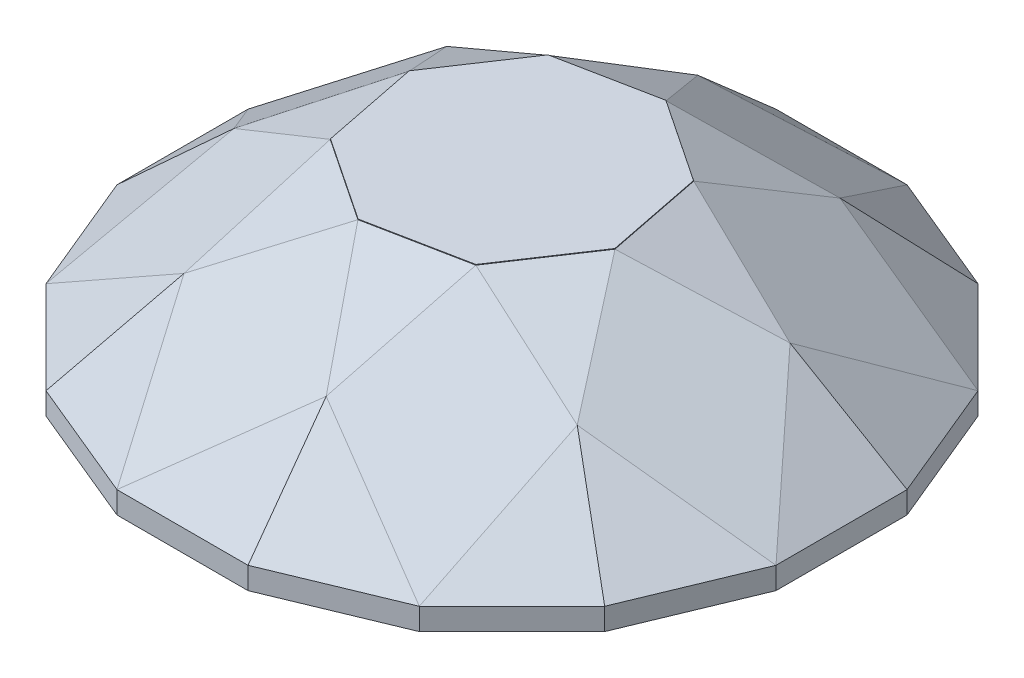
SolidWorks part; units mm, degrees
material "Pure Gold"
ref_plane "Front Plane" through (0, 0, 0) normal (0, 0, 1) x (1, 0, 0)
ref_plane "Top Plane" through (0, 0, 0) normal (0, 1, 0) x (1, 0, 0)
ref_plane "Right Plane" through (0, 0, 0) normal (1, 0, 0) x (0, 0, -1)
sketch "Sketch1" plane through (0, 0, 0) normal (0, 1, 0) x (1, 0, 0)
  line L0 (1.5, 0.2984) -> (1.2716, 0.8497)
  line L1 (-0.8497, -1.2716) -> (-0.2984, -1.5)
  line L2 (-0.2984, -1.5) -> (0.2984, -1.5)
  line L3 (0.2984, -1.5) -> (0.8497, -1.2716)
  line L4 (0.8497, -1.2716) -> (1.2716, -0.8497)
  line L5 (1.2716, -0.8497) -> (1.5, -0.2984)
  line L6 (1.5, -0.2984) -> (1.5, 0.2984)
  line L7 (1.2716, 0.8497) -> (0.8497, 1.2716)
  line L8 (0.8497, 1.2716) -> (0.2984, 1.5)
  line L9 (0.2984, 1.5) -> (-0.2984, 1.5)
  line L10 (-0.2984, 1.5) -> (-0.8497, 1.2716)
  line L11 (-0.8497, 1.2716) -> (-1.2716, 0.8497)
  line L12 (-1.2716, 0.8497) -> (-1.5, 0.2984)
  line L13 (-1.5, 0.2984) -> (-1.5, -0.2984)
  line L14 (-1.5, -0.2984) -> (-1.2716, -0.8497)
  line L15 (-1.2716, -0.8497) -> (-0.8497, -1.2716)
  circle A0 centre (0, 0) radius 1.5 construction
  dimension "D1" = 3
extrude "Boss-Extrude1" add sketch "Sketch1" against normal blind 1 draft 57
sketch "Sketch2" plane through (0, 0, 0) normal (0, 1, 0) x (1, 0, 0)
  line L16 (-1.2716, -0.8497) -> (-0.8497, -1.2716)
  line L17 (-0.8497, -1.2716) -> (-0.2984, -1.5)
  line L18 (-0.2984, -1.5) -> (0.2984, -1.5)
  line L19 (0.2984, -1.5) -> (0.8497, -1.2716)
  line L20 (0.8497, -1.2716) -> (1.2716, -0.8497)
  line L21 (1.2716, -0.8497) -> (1.5, -0.2984)
  line L22 (1.5, -0.2984) -> (1.5, 0.2984)
  line L23 (1.5, 0.2984) -> (1.2716, 0.8497)
  line L24 (1.2716, 0.8497) -> (0.8497, 1.2716)
  line L25 (0.8497, 1.2716) -> (0.2984, 1.5)
  line L26 (0.2984, 1.5) -> (-0.2984, 1.5)
  line L27 (-0.2984, 1.5) -> (-0.8497, 1.2716)
  line L28 (-0.8497, 1.2716) -> (-1.2716, 0.8497)
  line L29 (-1.2716, 0.8497) -> (-1.5, 0.2984)
  line L30 (-1.5, 0.2984) -> (-1.5, -0.2984)
  line L31 (-1.5, -0.2984) -> (-1.2716, -0.8497)
  line L32 (-1.2716, -0.8497) -> (-0.8497, -1.2716)
  line L33 (-0.8497, -1.2716) -> (-0.2984, -1.5)
  line L34 (-0.2984, -1.5) -> (0.2984, -1.5)
  line L35 (0.2984, -1.5) -> (0.8497, -1.2716)
  line L36 (0.8497, -1.2716) -> (1.2716, -0.8497)
  line L37 (1.2716, -0.8497) -> (1.5, -0.2984)
  line L38 (1.5, -0.2984) -> (1.5, 0.2984)
  line L39 (1.5, 0.2984) -> (1.2716, 0.8497)
  line L40 (1.2716, 0.8497) -> (0.8497, 1.2716)
  line L41 (0.8497, 1.2716) -> (0.2984, 1.5)
  line L42 (0.2984, 1.5) -> (-0.2984, 1.5)
  line L43 (-0.2984, 1.5) -> (-0.8497, 1.2716)
  line L44 (-0.8497, 1.2716) -> (-1.2716, 0.8497)
  line L45 (-1.2716, 0.8497) -> (-1.5, 0.2984)
  line L46 (-1.5, 0.2984) -> (-1.5, -0.2984)
  line L47 (-1.5, -0.2984) -> (-1.2716, -0.8497)
  dimension "D1" = 0
extrude "Boss-Extrude2" add sketch "Sketch2" along normal blind 0.1
sketch "Sketch3" plane through (0, 0.1, 0) normal (0, 1, 0) x (1, 0, 0)
  line L16 (-1.5, -0.2984) -> (-1.2716, -0.8497)
  line L17 (-1.2716, -0.8497) -> (-0.8497, -1.2716)
  line L18 (-0.8497, -1.2716) -> (-0.2984, -1.5)
  line L19 (-0.2984, -1.5) -> (0.2984, -1.5)
  line L20 (0.2984, -1.5) -> (0.8497, -1.2716)
  line L21 (0.8497, -1.2716) -> (1.2716, -0.8497)
  line L22 (1.2716, -0.8497) -> (1.5, -0.2984)
  line L23 (1.5, -0.2984) -> (1.5, 0.2984)
  line L24 (1.5, 0.2984) -> (1.2716, 0.8497)
  line L25 (1.2716, 0.8497) -> (0.8497, 1.2716)
  line L26 (0.8497, 1.2716) -> (0.2984, 1.5)
  line L27 (0.2984, 1.5) -> (-0.2984, 1.5)
  line L28 (-0.2984, 1.5) -> (-0.8497, 1.2716)
  line L29 (-0.8497, 1.2716) -> (-1.2716, 0.8497)
  line L30 (-1.2716, 0.8497) -> (-1.5, 0.2984)
  line L31 (-1.5, 0.2984) -> (-1.5, -0.2984)
  line L32 (-1.5, -0.2984) -> (-1.2716, -0.8497)
  line L33 (-1.2716, -0.8497) -> (-0.8497, -1.2716)
  line L34 (-0.8497, -1.2716) -> (-0.2984, -1.5)
  line L35 (-0.2984, -1.5) -> (0.2984, -1.5)
  line L36 (0.2984, -1.5) -> (0.8497, -1.2716)
  line L37 (0.8497, -1.2716) -> (1.2716, -0.8497)
  line L38 (1.2716, -0.8497) -> (1.5, -0.2984)
  line L39 (1.5, -0.2984) -> (1.5, 0.2984)
  line L40 (1.5, 0.2984) -> (1.2716, 0.8497)
  line L41 (1.2716, 0.8497) -> (0.8497, 1.2716)
  line L42 (0.8497, 1.2716) -> (0.2984, 1.5)
  line L43 (0.2984, 1.5) -> (-0.2984, 1.5)
  line L44 (-0.2984, 1.5) -> (-0.8497, 1.2716)
  line L45 (-0.8497, 1.2716) -> (-1.2716, 0.8497)
  line L46 (-1.2716, 0.8497) -> (-1.5, 0.2984)
  line L47 (-1.5, 0.2984) -> (-1.5, -0.2984)
  dimension "D1" = 0
extrude "Boss-Extrude3" add sketch "Sketch3" along normal blind 0.4 draft 48
sketch "Sketch4" plane through (0, 0.5, 0) normal (0, 1, 0) x (1, 0, 0)
  line L16 (-1.0558, 0.21) -> (-1.0558, -0.21)
  line L17 (-1.0558, -0.21) -> (-0.895, -0.598)
  line L18 (-0.895, -0.598) -> (-0.598, -0.895)
  line L19 (-0.598, -0.895) -> (-0.21, -1.0558)
  line L20 (-0.21, -1.0558) -> (0.21, -1.0558)
  line L21 (0.21, -1.0558) -> (0.598, -0.895)
  line L22 (0.598, -0.895) -> (0.895, -0.598)
  line L23 (0.895, -0.598) -> (1.0558, -0.21)
  line L24 (1.0558, -0.21) -> (1.0558, 0.21)
  line L25 (1.0558, 0.21) -> (0.895, 0.598)
  line L26 (0.895, 0.598) -> (0.598, 0.895)
  line L27 (0.598, 0.895) -> (0.21, 1.0558)
  line L28 (0.21, 1.0558) -> (-0.21, 1.0558)
  line L29 (-0.21, 1.0558) -> (-0.598, 0.895)
  line L30 (-0.598, 0.895) -> (-0.895, 0.598)
  line L31 (-0.895, 0.598) -> (-1.0558, 0.21)
  line L32 (-1.0558, 0.21) -> (-1.0558, -0.21)
  line L33 (-1.0558, -0.21) -> (-0.895, -0.598)
  line L34 (-0.895, -0.598) -> (-0.598, -0.895)
  line L35 (-0.598, -0.895) -> (-0.21, -1.0558)
  line L36 (-0.21, -1.0558) -> (0.21, -1.0558)
  line L37 (0.21, -1.0558) -> (0.598, -0.895)
  line L38 (0.598, -0.895) -> (0.895, -0.598)
  line L39 (0.895, -0.598) -> (1.0558, -0.21)
  line L40 (1.0558, -0.21) -> (1.0558, 0.21)
  line L41 (1.0558, 0.21) -> (0.895, 0.598)
  line L42 (0.895, 0.598) -> (0.598, 0.895)
  line L43 (0.598, 0.895) -> (0.21, 1.0558)
  line L44 (0.21, 1.0558) -> (-0.21, 1.0558)
  line L45 (-0.21, 1.0558) -> (-0.598, 0.895)
  line L46 (-0.598, 0.895) -> (-0.895, 0.598)
  line L47 (-0.895, 0.598) -> (-1.0558, 0.21)
  dimension "D1" = 0
extrude "Boss-Extrude4" add sketch "Sketch4" along normal blind 0.3
sketch "Sketch5" plane through (0.276, 0.8011, 0.6664) normal (0.2561, 0.7431, 0.6182) x (0.9667, -0.1969, -0.1638)
  line L0 (-0.0683, -0.4919) -> (0.5934, -0.9137)
sketch "Sketch6" plane through (0.5101, 0.8011, 0.5101) normal (0.4731, 0.7431, 0.4731) x (0.881, -0.3991, -0.2541)
  line L0 (0.3855, -1.019) -> (0.437, -0.2359)
ref_plane "Plane1" through (0.3314, 0.7976, 0.496) normal (0.3327, 0.8008, 0.498) x (0.943, -0.2826, -0.1757)
sketch "Sketch7" plane through (0.3314, 0.7976, 0.496) normal (0.3327, 0.8008, 0.498) x (0.943, -0.2826, -0.1757)
  line L0 (0.5496, -1.0271) -> (0.5977, -0.2438) construction
  line L1 (-0.1287, -0.6326) -> (0.5496, -1.0271) construction
  line L2 (0.5496, -1.0271) -> (0.5977, -0.2438)
  line L3 (-0.1287, -0.6326) -> (0.5496, -1.0271)
  line L4 (-0.1287, -0.6326) -> (0, 0)
  line L5 (0, 0) -> (0.5977, -0.2438)
extrude "Cut-Extrude1" cut sketch "Sketch7" along normal blind 0.3
sketch "Sketch8" plane through (0, 0.8, 0) normal (0, 1, 0) x (1, 0, 0)
  point P0 (0, 0)
ref_axis "Axis1" through (0, -0.9741, 0) along (0, 1, 0)
pattern_circular "CirPattern1" count 8 over 360 about axis through (0, -0.9741, 0) along (0, 1, 0) of "Cut-Extrude1"
sketch "Sketch9" plane through (-0.3314, 0.7976, -0.496) normal (-0.3327, 0.8008, -0.498) x (0.943, 0.2826, -0.1757)
  line L0 (0.1287, 0.6326) -> (0, 0)
sketch "Sketch10" plane through (0.1164, 0.7976, -0.585) normal (0.1168, 0.8008, -0.5874) x (0.9932, -0.0942, 0.0691)
  line L0 (-0.3286, 0.5556) -> (0, 0)
ref_plane "Plane2" through (-0.0929, 0.8402, -0.4669) normal (-0.0962, 0.8701, -0.4835) x (0.9954, 0.0841, -0.0467)
sketch "Sketch11" plane through (-0.0929, 0.8402, -0.4669) normal (-0.0962, 0.8701, -0.4835) x (0.9954, 0.0841, -0.0467)
  line L0 (-0.1177, 0.68) -> (0.2102, 0.124) construction
  line L1 (-0.1177, 0.68) -> (-0.2396, 0.0461) construction
  line L2 (-0.1177, 0.68) -> (0.2102, 0.124)
  line L3 (-0.1177, 0.68) -> (-0.2396, 0.0461)
  line L4 (0.2102, 0.124) -> (-0.2396, 0.0461)
extrude "Cut-Extrude2" cut sketch "Sketch11" along normal blind 0.5 draft 46 draft outward yes
pattern_circular "CirPattern2" count 8 over 360 about axis through (0, -0.9741, 0) along (0, 1, 0) of "Cut-Extrude2"
